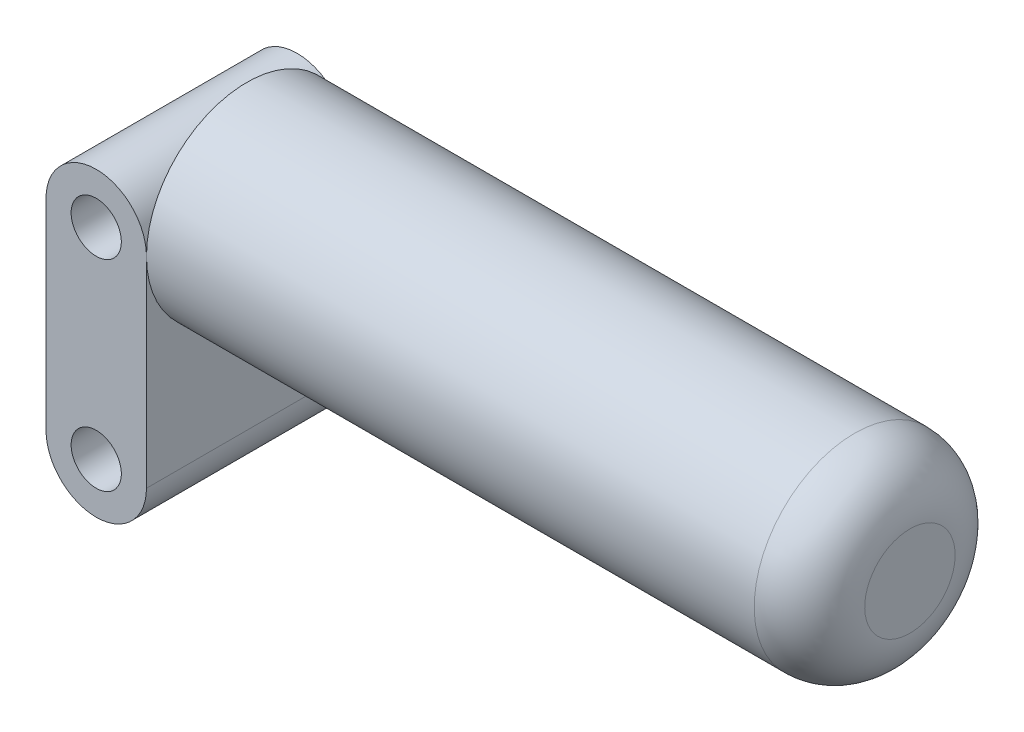
SolidWorks part; units mm, degrees
ref_plane "Plan de face" through (0, 0, 0) normal (0, 0, 1) x (1, 0, 0)
ref_plane "Plan de dessus" through (0, 0, 0) normal (0, 1, 0) x (1, 0, 0)
ref_plane "Plan de droite" through (0, 0, 0) normal (1, 0, 0) x (0, 0, -1)
other "Centre de masse"
sketch "Esquisse1" plane through (0, 0, 0) normal (0, 0, 1) x (1, 0, 0)
  line L0 (0, 10) -> (0, -10) construction
  line L1 (5, 10) -> (5, -10)
  line L2 (-5, 10) -> (-5, -10)
  line L3 (0, 0) -> (16.4339, 0) construction
  arc A0 (5, 10) -> (-5, 10) centre (0, 10) ccw
  arc A1 (-5, -10) -> (5, -10) centre (0, -10) ccw
  circle A2 centre (0, 10) radius 2.5
  circle A3 centre (0, -10) radius 2.5
  point P3 (0, 0)
  dimension "D3" = 5
  dimension "D2" = 10
extrude "Boss.-Extru.1" add sketch "Esquisse1" along normal mid plane 20
sketch "Esquisse2" plane through (5, 0, 0) normal (1, 0, 0) x (0, 0, -1)
  line L0 (0, 11.352) -> (0, 0) construction
  line L1 (0, 0) -> (4.254, 0) construction
  circle A0 centre (0, 10) radius 10
  dimension "D1" = 20
extrude "Boss.-Extru.2" add sketch "Esquisse2" along normal blind 66 contours A0
fillet "Congé1" radius 5.5 1 edges at (71, 20, 0)
ref_axis "Axe1" through (0, 10, 10) along (0, 0, -1)
ref_point "Point1"
equation "\"e\"= 0.02m"
equation "\"d\"= 0.05"
equation "\"l\"= 0.01"
equation "\"D2@Esquisse1\"=\"l\""
equation "\"D1@Boss.-Extru.1\"=\"e\""
equation "\"Ddoigt\"= 0.02m"
equation "\"D1@Esquisse2\"=\"Ddoigt\""
equation "\"Ldoigt\"= 0.066m"
equation "\"D1@Boss.-Extru.2\"=\"Ldoigt\""
equation "\"D1@Congé1\"=\"Ldoigt\"/12m"
